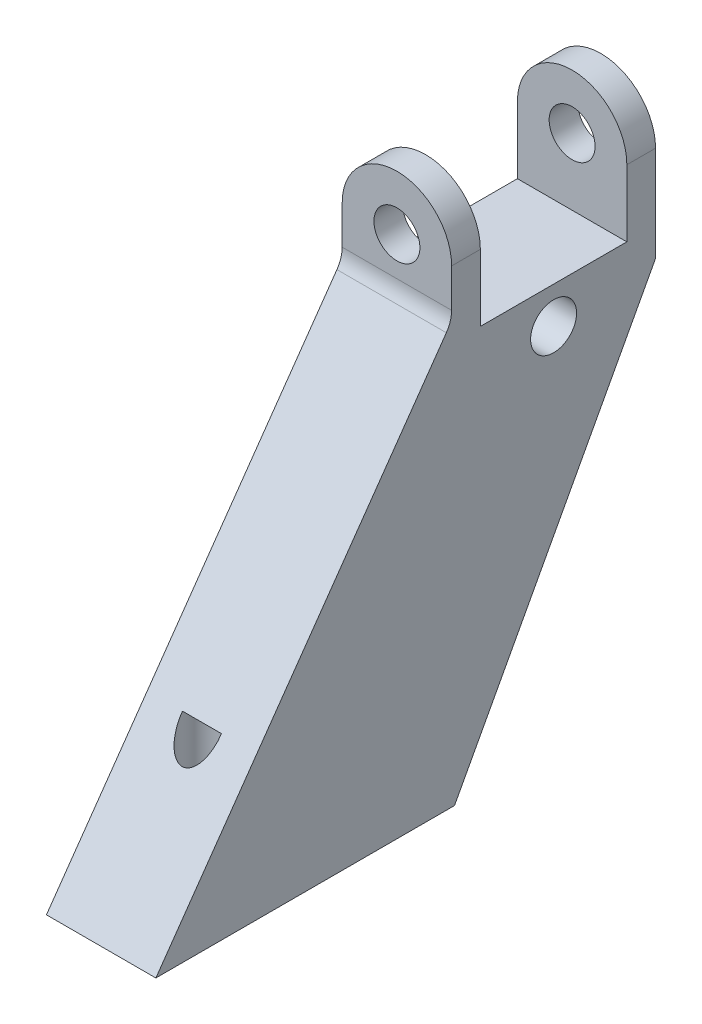
SolidWorks part; units mm, degrees
ref_plane "Front Plane" through (0, 0, 0) normal (0, 0, 1) x (1, 0, 0)
ref_plane "Top Plane" through (0, 0, 0) normal (0, 1, 0) x (1, 0, 0)
ref_plane "Right Plane" through (0, 0, 0) normal (1, 0, 0) x (0, 0, -1)
sketch "Sketch6" plane through (0, 3.4314, 0) normal (0, 1, 0) x (-1, 0, 0)
  line L0 (-13.5144, 0) -> (5.5356, 0)
  line L5 (-7.9894, 155.54) -> (0.0106, 155.54) construction
  line L8 (5.5356, 0) -> (5.5356, 133.908)
  line L9 (5.5356, 133.908) -> (-13.5144, 133.908)
  line L10 (-13.5144, 0) -> (-13.5144, 133.908)
  line L17 (-7.9894, 155.54) -> (0.0106, 155.54) construction
  line L18 (-3.9894, 155.54) -> (-3.9894, 0) construction
  dimension "D1" = 19.05
sketch3d "3DSketch1" [suppressed]
  circle A0 centre (4.1661, 92.3902, 4.7625) radius 4 construction
  circle A1 centre (4.1661, 92.3902, 4.7625) radius 4
  circle A2 centre (4.1661, 92.3902, 30.1625) radius 4 construction
  circle A3 centre (4.1661, 92.3902, 30.1625) radius 4
  point P2 (4.1661, 92.3902, 8.7625)
  point P4 (4.1661, 92.3902, 8.7625)
  point P7 (4.1661, 92.3902, 34.1625)
  point P9 (4.1661, 92.3902, 34.1625)
extrude "Boss-Extrude5" add sketch "Sketch6" along normal blind 101.6
sketch "Sketch9" plane through (0, 0, 0) normal (0, 0, -1) x (-1, 0, 0)
  line L1 (-13.5144, 105.0314) -> (6.0586, 105.0314)
  line L2 (-13.5144, 105.0314) -> (-13.5144, 87.861)
  line L3 (-13.5144, 87.861) -> (6.0586, 87.861)
  line L12 (6.0586, 105.0314) -> (6.0586, 87.861)
extrude "Cut-Extrude5" [suppressed] cut sketch "Sketch9" against normal through all
sketch "Sketch10" plane through (13.5144, 0, 0) normal (1, 0, 0) x (0, 0, -1)
  line L0 (-87, 3.4314) -> (-167.5984, 3.4314)
  line L1 (-133.908, 3.4314) -> (0, 3.4314) construction
  line L2 (-167.5984, 3.4314) -> (-168.5558, 132.8824)
  line L3 (-168.5558, 132.8824) -> (-35.5045, 117.0228)
  line L4 (-35.5045, 117.0228) -> (-35.5045, 78.3573)
  line L5 (-36.4274, 75.4376) -> (-87, 3.4314)
  line L6 (-35, 3.4314) -> (7.4334, 3.4314)
  line L7 (7.4334, 3.4314) -> (7.4334, 68.4314)
  line L8 (7.4334, 68.4314) -> (0, 68.4314)
  line L9 (0, 68.4314) -> (-35, 3.4314)
  line L10 (0, 105.0314) -> (0, 3.4314) construction
  line L12 (-30.5045, 96.7069) -> (-5, 96.7069)
  line L13 (-30.5045, 96.7069) -> (-30.5045, 73.4314)
  line L14 (-30.5045, 73.4314) -> (-5, 73.4314)
  line L15 (-5, 96.7069) -> (-5, 73.4314)
  arc A0 (-35.5045, 78.3573) -> (-36.4274, 75.4376) centre (-40.5845, 78.3573) cw
  point P12 (-35.5045, 76.7516)
  point P22 (-30.5045, 85.0692)
  dimension "D8" = 5.08
  dimension "D1" = 5
  dimension "D2" = 5
  dimension "D3" = 65
  dimension "D4" = 35
  dimension "D5" = 52
  dimension "D6" = 25.5045
  dimension "D7" = 70
extrude "Cut-Extrude6" cut sketch "Sketch10" against normal through all
sketch "Sketch12" plane through (0, 0, 35.5045) normal (0, 0, 1) x (1, 0, 0)
  line L0 (3.9894, 3.4314) -> (3.9894, 85.0528) construction
  line L1 (7.9894, 3.4314) -> (-0.0106, 3.4314) construction
  line L2 (-5.5356, 85.0528) -> (13.5144, 85.0528) construction
  line L3 (-5.5356, 78.3573) -> (-5.5356, 105.0314) construction
  line L4 (13.5144, 78.3573) -> (13.5144, 105.0314) construction
  line L5 (13.5144, 85.0528) -> (39.9433, 85.0528)
  line L6 (39.9433, 85.0528) -> (39.9433, 114.8081)
  line L7 (39.9433, 114.8081) -> (-16.1264, 114.8081)
  line L8 (-16.1264, 114.8081) -> (-16.1264, 85.0528)
  line L9 (-16.1264, 85.0528) -> (-5.5356, 85.0528)
  circle A0 centre (3.9894, 85.0528) radius 4
  arc A1 (13.5144, 85.0528) -> (-5.5356, 85.0528) centre (3.9894, 85.0528) ccw
  dimension "D2" = 8
  dimension "D1" = 81.6214
extrude "Cut-Extrude7" cut sketch "Sketch12" against normal through all
sketch "Sketch13" plane through (0, 3.4314, 0) normal (0, -1, 0) x (1, 0, 0)
  line L0 (3.9894, 87) -> (3.9894, 69.5) construction
  line L1 (-5.5356, 87) -> (13.5144, 87) construction
  line L2 (3.9894, 155.54) -> (3.9894, 0) construction
  line L3 (3.9894, 69.5) -> (3.9894, 42.5) construction
  dimension "D1" = 17.5
  dimension "D2" = 27
sketch "Sketch14" plane through (0, 3.4314, 0) normal (0, -1, 0) x (1, 0, 0)
  circle A0 centre (3.9894, 69.5) radius 3.4
  circle A1 centre (3.9894, 42.5) radius 3.4
  dimension "D1" = 6.8
extrude "Cut-Extrude8" cut sketch "Sketch14" against normal blind 25
thread "Thread1" pitch 1.25 method cut profile "Thread Profile1" start angle 0, offset 0, length 15, pitch 1.25, diameter 6.8
ref_plane "Plane1" through (7.3894, 3.4314, 42.5) normal (0, 0, 1) x (1, 0, 0)
sketch "Thread Profile1" plane through (7.3894, 3.4314, 42.5) normal (0, 0, 1) x (1, 0, 0)
  line L0 (0, 0) -> (0, 1.25) construction
  line L1 (0, 0) -> (0.6766, 0.3906)
  line L2 (0.6766, 0.3906) -> (0.6766, 0.5469)
  line L3 (0.6766, 0.5469) -> (0, 0.9375)
  line L4 (0.6766, 0.4687) -> (0, 0.4687) construction
  line L11 (0, 0) -> (0, 0.9375)
  point P2 (0, 0)
  dimension "Pitch" = 1.25
  dimension "Profile_Angle" = 60
  dimension "Profile_Land" = 0.1562
  dimension "Profile_Height" = 0.6766
thread "Thread2" pitch 1.25 method cut profile "Thread Profile2" start angle 0, offset 0, length 15, pitch 1.25, diameter 6.8
ref_plane "Plane2" through (7.3894, 3.4314, 69.5) normal (0, 0, 1) x (1, 0, 0)
sketch "Thread Profile2" plane through (7.3894, 3.4314, 69.5) normal (0, 0, 1) x (1, 0, 0)
  line L0 (0, 0) -> (0, 1.25) construction
  line L1 (0, 0) -> (0.6766, 0.3906)
  line L2 (0.6766, 0.3906) -> (0.6766, 0.5469)
  line L3 (0.6766, 0.5469) -> (0, 0.9375)
  line L4 (0.6766, 0.4687) -> (0, 0.4687) construction
  line L11 (0, 0) -> (0, 0.9375)
  point P2 (0, 0)
  dimension "Pitch" = 1.25
  dimension "Profile_Angle" = 60
  dimension "Profile_Land" = 0.1562
  dimension "Profile_Height" = 0.6766
sketch "Sketch19" plane through (13.5144, 0, 0) normal (1, 0, 0) x (0, 0, -1)
  line L0 (-17.7522, 73.4314) -> (-17.7522, 67.0814) construction
  line L1 (-30.5045, 73.4314) -> (-5, 73.4314) construction
  circle A0 centre (-17.7522, 67.0814) radius 4
  point P6 (0, 0)
  dimension "D1" = 6.35
  dimension "D2" = 8
extrude "Cut-Extrude9" cut sketch "Sketch19" against normal through all
